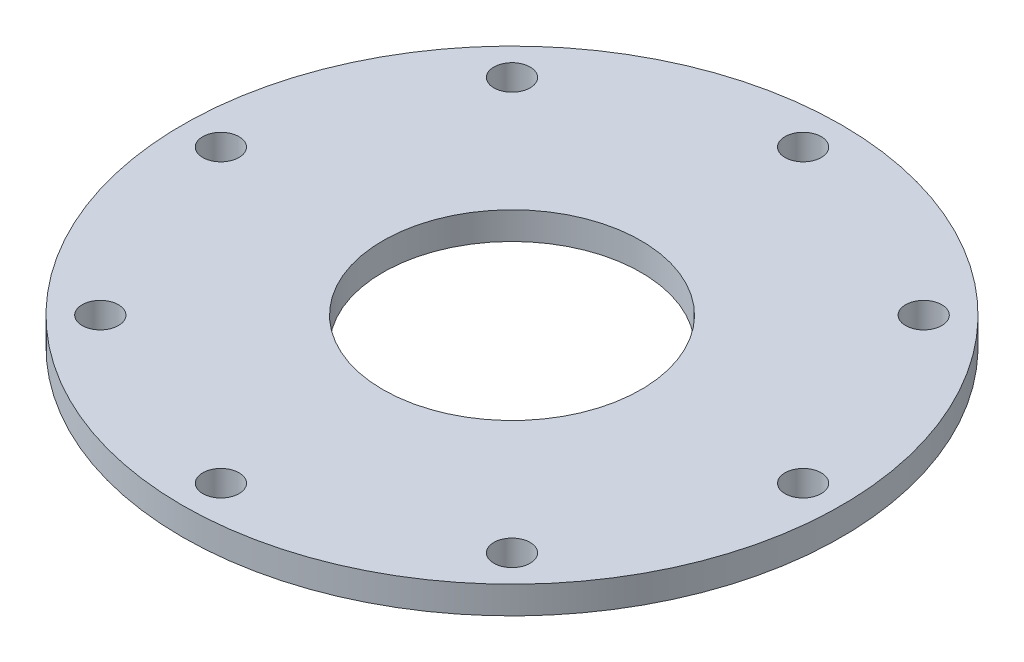
SolidWorks part; units mm, degrees
ref_plane "Front Plane" through (0, 0, 0) normal (0, 0, 1) x (1, 0, 0)
ref_plane "Top Plane" through (0, 0, 0) normal (0, 1, 0) x (1, 0, 0)
ref_plane "Right Plane" through (0, 0, 0) normal (1, 0, 0) x (0, 0, -1)
sketch "Sketch1" plane through (0, 0, 0) normal (0, 1, 0) x (1, 0, 0)
  circle A0 centre (0, 0) radius 60
  circle A1 centre (0, 0) radius 23.5
  dimension "D1" = 120
  dimension "D2" = 47
extrude "Boss-Extrude1" add sketch "Sketch1" along normal blind 5
sketch "Sketch4" plane through (0, 5, 0) normal (0, 1, 0) x (1, 0, 0)
  circle A1 centre (0, 0) radius 60
  circle A2 centre (0, 0) radius 60 construction
  circle A3 centre (0, 0) radius 53 construction
  point P5 (0, 53)
  point P6 (37.4767, 37.4767)
  point P9 (53, 0)
  point P10 (37.4767, -37.4767)
  point P11 (0, -53)
  point P12 (-37.4767, -37.4767)
  point P13 (-53, 0)
  point P14 (-37.4767, 37.4767)
  dimension "D2" = 106
  dimension "D1" = 0
  dimension "D3" = 8
hole_wizard "M6 Clearance Hole1" positions "Sketch4" profile "Sketch5" hole size "M6" standard "ISO" end condition through all
sketch "Sketch5" plane through (-37.4767, 5, -37.4767) normal (1, 0, 0) x (0, 0, 1)
  line L0 (0, 0) -> (0, 5)
  line L1 (0, 5) -> (3.3, 5)
  line L2 (3.3, 5) -> (3.3, 0)
  line L5 (3.3, 0) -> (0, 0)
  line L11 (0, -6.35) -> (0, 107.95) construction
  dimension "Thru Hole Dia." = 6.6
  dimension "Thru Hole Depth" = 5
